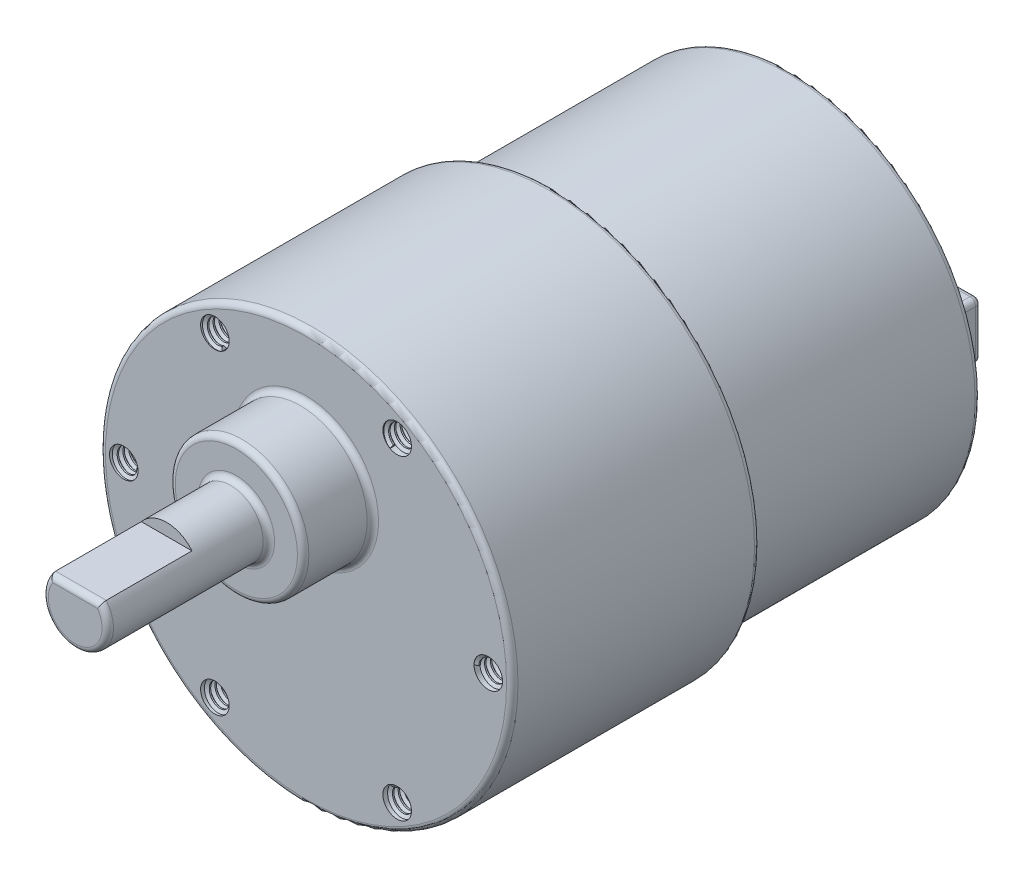
SolidWorks part; units mm, degrees
ref_plane "Front Plane" through (0, 0, 0) normal (0, 0, 1) x (1, 0, 0)
ref_plane "Top Plane" through (0, 0, 0) normal (0, 1, 0) x (1, 0, 0)
ref_plane "Right Plane" through (0, 0, 0) normal (1, 0, 0) x (0, 0, -1)
sketch "Sketch1" plane through (0, 0, 0) normal (0, 0, 1) x (1, 0, 0)
  circle A0 centre (0, 0) radius 16.45
  dimension "D1" = 32.9
extrude "Boss-Extrude1" add sketch "Sketch1" along normal blind 20.9
sketch "Sketch2" plane through (0, 0, 20.9) normal (0, 0, 1) x (1, 0, 0)
  circle A0 centre (0, 0) radius 18.05
  dimension "D1" = 36.1
extrude "Boss-Extrude2" add sketch "Sketch2" along normal blind 21.7
sketch "Sketch3" plane through (0, 0, 0) normal (0, 0, -1) x (-1, 0, 0)
  circle A0 centre (0, 0) radius 3.7
  dimension "D1" = 7.4
extrude "Boss-Extrude3" add sketch "Sketch3" along normal blind 2.9
sketch "Sketch4" plane through (0, 0, 0) normal (0, 0, -1) x (-1, 0, 0)
  line L1 (-11.5, 2.5) -> (-8.5, 2.5)
  line L2 (-11.5, 2.5) -> (-11.5, -2.5)
  line L3 (-11.5, -2.5) -> (-8.5, -2.5)
  line L4 (-8.5, 2.5) -> (-8.5, -2.5)
  line L5 (-11.5, 2.5) -> (-8.5, -2.5) construction
  line L6 (-11.5, -2.5) -> (-8.5, 2.5) construction
  line L7 (8.5, 2.5) -> (11.5, 2.5)
  line L8 (8.5, 2.5) -> (8.5, -2.5)
  line L9 (8.5, -2.5) -> (11.5, -2.5)
  line L10 (11.5, 2.5) -> (11.5, -2.5)
  line L11 (8.5, 2.5) -> (11.5, -2.5) construction
  line L12 (8.5, -2.5) -> (11.5, 2.5) construction
  point P0 (-10, 0)
  point P5 (10, 0)
  point P10 (10, 0)
  point P12 (-10, 0)
  dimension "D1" = 3
  dimension "D2" = 5
  dimension "D3" = 3
  dimension "D4" = 5
  dimension "D5" = 10
  dimension "D6" = 10
extrude "Boss-Extrude4" add sketch "Sketch4" along normal blind 5
sketch "Sketch5" plane through (0, 0, 42.6) normal (0, 0, 1) x (1, 0, 0)
  circle A0 centre (0, 6.7) radius 5.85
  point P2 (0, 10.4254)
  point P3 (0, 0)
  dimension "D1" = 11.7
  dimension "D2" = 6.7
extrude "Boss-Extrude5" add sketch "Sketch5" along normal blind 6.1
sketch "Sketch6" plane through (0, 0, 48.7) normal (0, 0, 1) x (1, 0, 0)
  circle A0 centre (0, 6.7) radius 2.85
  dimension "D1" = 5.7
extrude "Boss-Extrude6" add sketch "Sketch6" along normal blind 14.1
sketch "Sketch7" plane through (0, 0, 62.8) normal (0, 0, 1) x (1, 0, 0)
  line L0 (-2.2144, 8.4942) -> (2.2144, 8.4942)
  circle A1 centre (0, 6.7) radius 2.85
  arc A2 (2.2144, 8.4942) -> (-2.2144, 8.4942) centre (0, 6.7) ccw
  dimension "D1" = 0
extrude "Cut-Extrude1" cut sketch "Sketch7" against normal blind 8
fillet "Fillet1" radius 0.5 35 edges at (0, 3.85, 62.8) (0, 8.4942, 62.8) (2.85, 6.7, 48.7) (5.85, 6.7, 48.7) (5.85, 6.7, 42.6) (-8.5, -2.5, -2.5) (-8.5, 2.5, -2.5) (-11.5, -2.5, -2.5) (-11.5, 2.5, -2.5) (-10, -2.5, -5) (-8.5, 0, -5) (-10, 2.5, -5) (-11.5, 0, -5) (8.5, -2.5, -2.5) (11.5, -2.5, -2.5) (10, -2.5, -5) (11.5, 0, -5) (8.5, 0, -5) (8.5, 2.5, -2.5) (10, 2.5, -5) (11.5, 2.5, -2.5) (-10, 2.5, 0) (-8.5, 0, 0) (-10, -2.5, 0) (-11.5, 0, 0) (10, 2.5, 0) (11.5, 0, 0) (10, -2.5, 0) (8.5, 0, 0) (-3.7, 0, 0) (-3.7, 0, -2.9) (16.45, 0, 0) (16.45, 0, 20.9) (18.05, 0, 20.9) (18.05, 0, 42.6)
sketch "Sketch8" plane through (0, 0, 42.6) normal (0, 0, 1) x (1, 0, 0)
  circle A0 centre (15.95, 0) radius 1.25
  circle A1 centre (0, 0) radius 18.05 construction
  circle A2 centre (7.975, -13.8131) radius 1.25
  circle A3 centre (-7.975, -13.8131) radius 1.25
  circle A4 centre (-15.95, 0) radius 1.25
  circle A5 centre (-7.975, 13.8131) radius 1.25
  circle A6 centre (7.975, 13.8131) radius 1.25
  point P5 (0, 0)
  point P16 (0, 0)
  dimension "D1" = 2.5
  dimension "D2" = 15.95
  dimension "D3" = 6
extrude "Cut-Extrude2" cut sketch "Sketch8" against normal blind 4
thread "Thread1" pitch 0.5 start angle 0, offset 0, length 0, pitch 0.5, diameter 2.5
ref_plane "Plane1" through (14.7, 0, 42.6) normal (0, -1, 0) x (-1, 0, 0)
sketch "Thread Profile1" plane through (14.7, 0, 42.6) normal (0, -1, 0) x (-1, 0, 0)
  line L0 (0, 0) -> (0, 0.5) construction
  line L11 (0, 0) -> (0, 0.4375)
  line L12 (0, 0.4375) -> (-0.2706, 0.2812)
  line L13 (-0.2706, 0.2812) -> (-0.2706, 0.1562)
  line L15 (-0.2706, 0.1562) -> (0, 0)
  line L17 (-0.2706, 0.2187) -> (0, 0.2187) construction
  point P2 (0, 0)
  dimension "Pitch" = 0.5
  dimension "Profile_Angle" = 60
  dimension "Profile_Land" = 0.125
  dimension "Profile_Height" = 0.2706
pattern_circular "CirPattern1" count 6 over 360 about axis through (0, 0, 42.6) along (0, 0, -1) of "Thread1"
